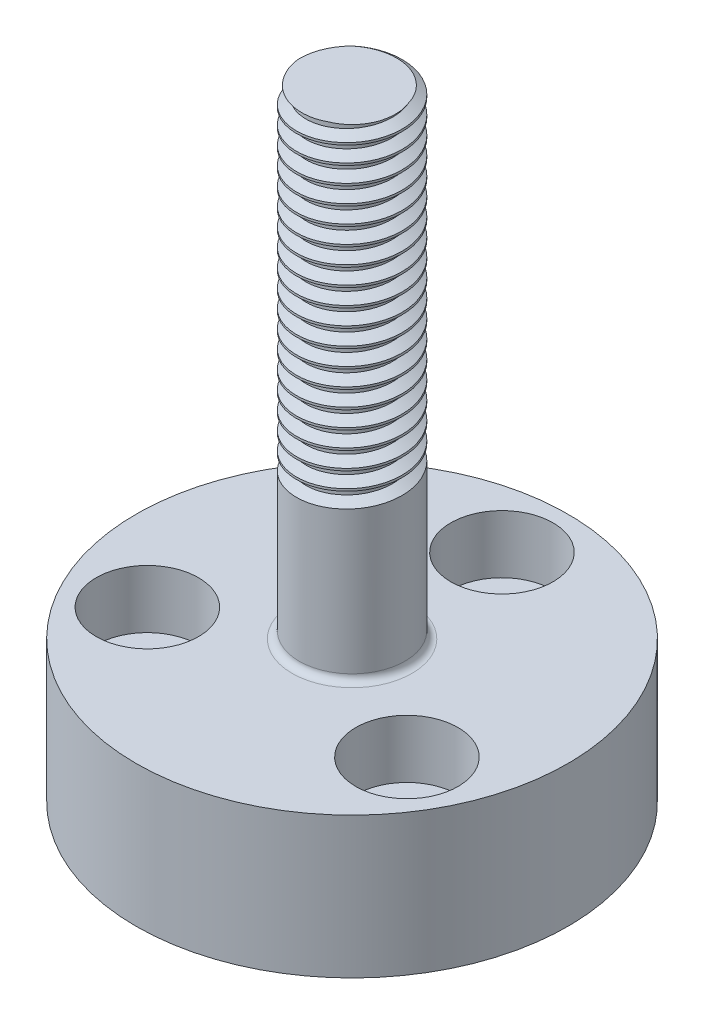
SolidWorks part; units mm, degrees
material "1060 Alloy"
ref_plane "Front Plane" through (0, 0, 0) normal (0, 0, 1) x (1, 0, 0)
ref_plane "Top Plane" through (0, 0, 0) normal (0, 1, 0) x (1, 0, 0)
ref_plane "Right Plane" through (0, 0, 0) normal (1, 0, 0) x (0, 0, -1)
sketch "Sketch2" plane through (0, 0, 0) normal (0, 1, 0) x (1, 0, 0)
  line L0 (0, 0) -> (0, 12.25) construction
  circle A0 centre (0, 0) radius 12.25
  circle A1 centre (0, 0) radius 8.5 construction
  circle A2 centre (0, 8.5) radius 1.6
  circle A3 centre (7.3612, -4.25) radius 1.6
  circle A4 centre (-7.3612, -4.25) radius 1.6
  dimension "D1" = 24.5
  dimension "D2" = 17
  dimension "D3" = 3.2
  dimension "D4" = 3
extrude "Boss-Extrude1" add sketch "Sketch2" along normal blind 8
sketch "Sketch3" plane through (0, 0, 0) normal (0, -1, 0) x (1, 0, 0)
  circle A0 centre (0, 0) radius 6
  dimension "D1" = 12
extrude "Cut-Extrude1" cut sketch "Sketch3" against normal blind 3
sketch "Sketch4" plane through (0, 8, 0) normal (0, 1, 0) x (1, 0, 0)
  circle A0 centre (0, 0) radius 3
  dimension "D1" = 6
extrude "Boss-Extrude2" add sketch "Sketch4" along normal blind 27
sketch "Sketch5" plane through (0, 8, 0) normal (0, 1, 0) x (1, 0, 0)
  circle A0 centre (7.3612, -4.25) radius 1.6 construction
  circle A1 centre (-7.3612, -4.25) radius 1.6 construction
  circle A2 centre (0, 8.5) radius 1.6 construction
  circle A3 centre (7.3612, -4.25) radius 1.6
  circle A4 centre (-7.3612, -4.25) radius 1.6
  circle A5 centre (0, 8.5) radius 1.6
  circle A6 centre (0, 8.5) radius 2.9
  circle A7 centre (-7.3612, -4.25) radius 2.9
  circle A8 centre (7.3612, -4.25) radius 2.9
  dimension "D1" = 5.8
extrude "Cut-Extrude2" cut sketch "Sketch5" against normal blind 3.3
fillet "Fillet1" radius 0.4 1 edges at (0, 8, 3)
thread "Thread1" pitch 1 method cut trim with start face yes trim with end face yes profile "Thread Profile1" start angle 0, offset 1, length 19, pitch 1, diameter 6
ref_plane "Plane1" through (-3, 36, 0) normal (0, 0, 1) x (-1, 0, 0)
sketch "Thread Profile1" plane through (-3, 36, 0) normal (0, 0, 1) x (-1, 0, 0)
  line L0 (0, 0) -> (0, 1) construction
  line L11 (0, 0) -> (0, 0.875)
  line L12 (0, 0.875) -> (-0.5413, 0.5625)
  line L13 (-0.5413, 0.5625) -> (-0.5413, 0.3125)
  line L15 (-0.5413, 0.3125) -> (0, 0)
  line L17 (-0.5413, 0.4375) -> (0, 0.4375) construction
  point P2 (0, 0)
  dimension "Pitch" = 1
  dimension "Profile_Angle" = 60
  dimension "Profile_Land" = 0.25
  dimension "Profile_Height" = 0.5413
